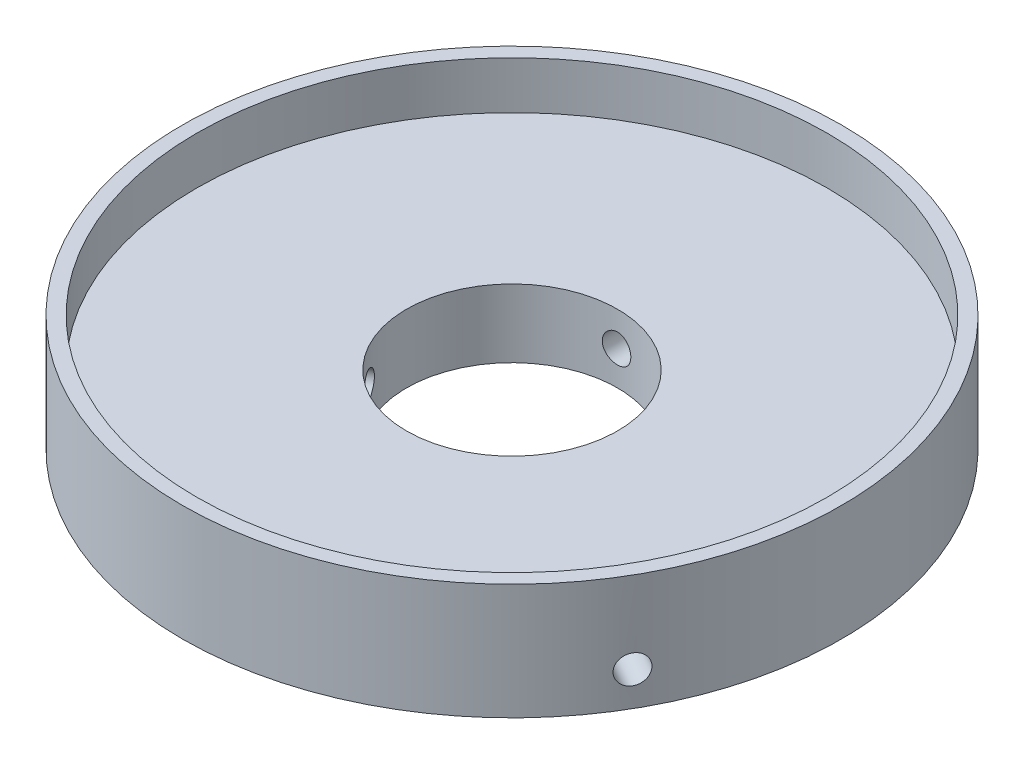
SolidWorks part; units mm, degrees
ref_plane "Front Plane" through (0, 0, 0) normal (0, 0, 1) x (1, 0, 0)
ref_plane "Top Plane" through (0, 0, 0) normal (0, 1, 0) x (1, 0, 0)
ref_plane "Right Plane" through (0, 0, 0) normal (1, 0, 0) x (0, 0, -1)
sketch "Sketch2" plane through (0, 0, 0) normal (0, 1, 0) x (1, 0, 0)
  circle A0 centre (0, 0) radius 33.1665
  circle A1 centre (0, 0) radius 11.1
  circle A2 centre (0, 0) radius 34.6665
  dimension "D1" = 66.333
  dimension "D2" = 22.2
  dimension "D3" = 1.5
extrude "Boss-Extrude1" add sketch "Sketch2" along normal blind 7.175 contours A0 A1 region at (-32.2284, 0, 0)
extrude "Boss-Extrude2" add sketch "Sketch2<5>" along normal blind 12.175 contours A2 A0 region at (-33.686, 0, 0)
sketch "Sketch2<5>" plane through (0, 0, 0) normal (0, 1, 0) x (1, 0, 0) same geometry as "Sketch2"
sketch "Sketch3" plane through (0, 0, 0) normal (0, -1, 0) x (1, 0, 0)
  line L0 (3.2928, 18) -> (-5.3006, 18) construction
  line L1 (2.5019, 18) -> (-2.5019, 18)
  arc A0 (-2.5019, 18) -> (2.5019, 18) centre (0, 18) ccw
  dimension "D1" = 18
revolve "Cut-Revolve1" cut sketch "Sketch3" angle 360 about L0
pattern_circular "CirPattern1" count 3 over 360 about axis through (0, 0, 0) along (0, 1, 0) of "Cut-Revolve1"
sketch "Sketch4" plane through (0, 0, 0) normal (0, -1, 0) x (1, 0, 0)
  line L0 (-15.5885, -9) -> (30.0221, 17.3332) construction
  circle A0 centre (0, 0) radius 34.6665 construction
ref_plane "Plane1" through (30.0221, 0, 17.3332) normal (0.866, 0, 0.5) x (0.5, 0, -0.866)
sketch "Sketch5" plane through (30.0221, 0, 17.3332) normal (0.866, 0, 0.5) x (0.5, 0, -0.866)
  circle A0 centre (0, 3.5875) radius 1.5
  dimension "D2" = 3
  dimension "D1" = 3.5875
extrude "Cut-Extrude3" cut sketch "Sketch5" against normal up to surface (23.6683 mm away) up to face at (0, 7.175, 11.1)
pattern_circular "CirPattern2" count 3 over 360 about axis through (0, 12.175, 0) along (0, -1, 0) of "Cut-Extrude3" reverse direction yes
